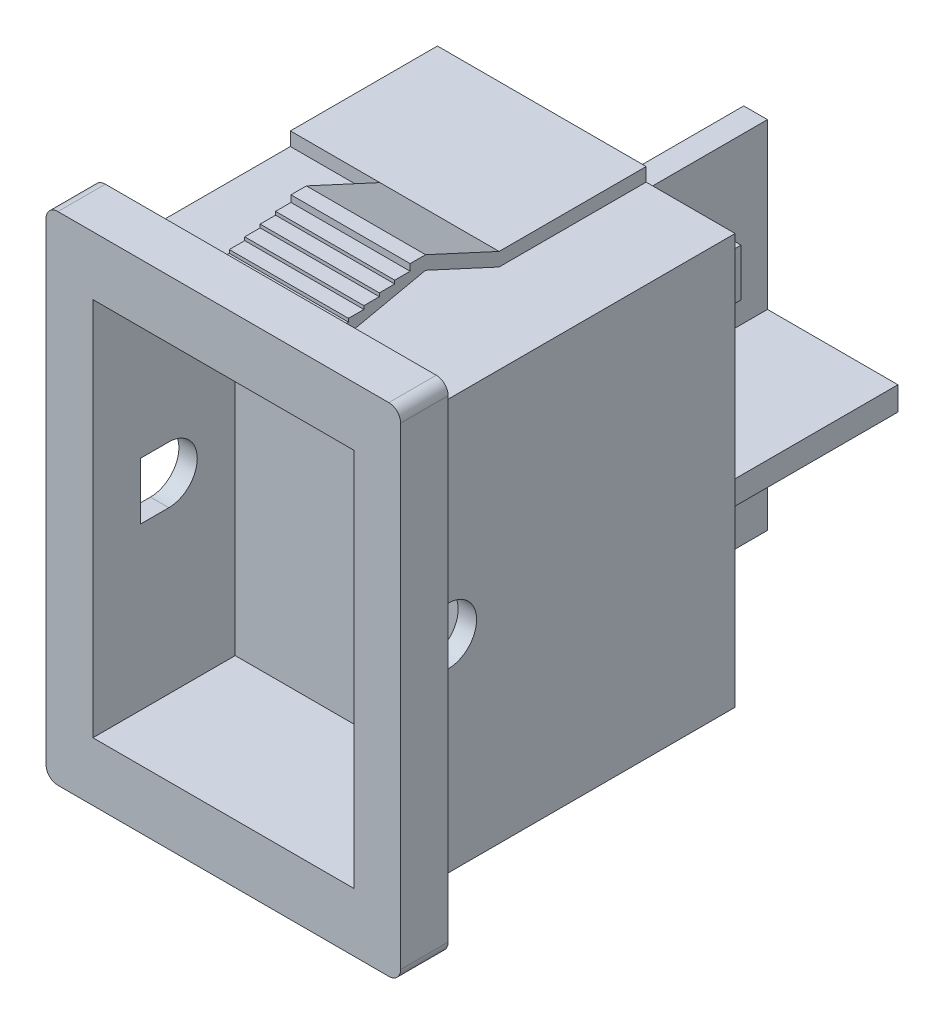
SolidWorks part; units mm, degrees
ref_plane "Front Plane" through (0, 0, 0) normal (0, 0, 1) x (1, 0, 0)
ref_plane "Top Plane" through (0, 0, 0) normal (0, 1, 0) x (1, 0, 0)
ref_plane "Right Plane" through (0, 0, 0) normal (1, 0, 0) x (0, 0, -1)
sketch "Sketch1" plane through (0, 0, 0) normal (0, 0, 1) x (1, 0, 0)
  line L1 (-7.475, 10.475) -> (7.475, 10.475)
  line L2 (-7.475, 10.475) -> (-7.475, -10.475)
  line L3 (-7.475, -10.475) -> (7.475, -10.475)
  line L4 (7.475, 10.475) -> (7.475, -10.475)
  line L5 (-5.5, 8) -> (5.5, 8)
  line L6 (-5.5, 8) -> (-5.5, -8)
  line L7 (-5.5, -8) -> (5.5, -8)
  line L8 (5.5, 8) -> (5.5, -8)
  dimension "D1" = 14.95
  dimension "D2" = 20.95
  dimension "D3" = 11
  dimension "D4" = 16
  dimension "D5" = 10.475
  dimension "D6" = 7.475
  dimension "D7" = 1.975
  dimension "D8" = 2.475
extrude "Boss-Extrude1" add sketch "Sketch1" along normal blind 2
sketch "Sketch2" plane through (0, 0, 0) normal (0, 0, -1) x (-1, 0, 0)
  line L1 (-6.275, 8.65) -> (6.275, 8.65)
  line L2 (-6.275, 8.65) -> (-6.275, -8.65)
  line L3 (-6.275, -8.65) -> (6.275, -8.65)
  line L4 (6.275, 8.65) -> (6.275, -8.65)
  dimension "D1" = 12.55
  dimension "D2" = 17.3
  dimension "D3" = 8.65
  dimension "D4" = 6.275
extrude "Boss-Extrude2" add sketch "Sketch2" along normal blind 13.3
sketch "Sketch3" plane through (-6.275, 0, 0) normal (-1, 0, 0) x (0, 0, 1)
  line L1 (-7.1, 9.22) -> (-13.3, 9.22)
  line L2 (-7.1, 9.22) -> (-7.1, -9.22)
  line L3 (-7.1, -9.22) -> (-13.3, -9.22)
  line L5 (-13.3, 9.22) -> (-13.3, -9.22)
  line L6 (-13.3, 8.65) -> (0, 8.65) construction
  line L7 (0, -8.65) -> (0, 8.65) construction
  line L9 (0, -8.65) -> (0, 8.65)
  line L10 (0, 8.65) -> (-13.3, 8.65)
  line L11 (-13.3, 8.65) -> (-13.3, -8.65)
  line L12 (-13.3, -8.65) -> (0, -8.65)
  line L15 (-13.3, 8.65) -> (-13.3, -8.65) construction
  dimension "D1" = 18.44
  dimension "D3" = 17.3
  dimension "D4" = 0.57
  dimension "D5" = 6.2
  dimension "D6" = 7.1
extrude "Boss-Extrude3" add sketch "Sketch3" against normal blind 8.8
ref_plane "Plane1" through (0, 0, 0) normal (1, 0, 0) x (0, 0, -1)
sketch "Sketch4" plane through (0, 0, 0) normal (1, 0, 0) x (0, 0, -1)
  line L0 (-4.4348, -10.65) -> (15.1231, -10.65) construction
  line L4 (4.9684, -10.65) -> (4.9684, 10.65) construction
  line L5 (-4.4348, 10.65) -> (15.1231, 10.65) construction
  line L6 (4, -13.528) -> (4, 14.734) construction
  line L7 (-5.6758, 0) -> (15.9446, 0) construction
  line L8 (7.1, -9.22) -> (4, -10.65)
  line L9 (7.1, -8.65) -> (4, -10.08)
  line L10 (0, -9.22) -> (4, -10.08)
  line L11 (0, -10.475) -> (0, 10.475) construction
  line L14 (4, -10.65) -> (3.35, -10.65)
  line L15 (2.7, -10.3705) -> (3.35, -10.3705)
  line L16 (3.35, -10.3705) -> (3.35, -10.65)
  line L17 (2.05, -10.2308) -> (2.7, -10.2308)
  line L18 (2.7, -10.2308) -> (2.7, -10.3705)
  line L19 (1.4, -10.091) -> (2.05, -10.091)
  line L20 (2.05, -10.091) -> (2.05, -10.2308)
  line L21 (0.75, -9.9513) -> (1.4, -9.9513)
  line L22 (1.4, -9.9513) -> (1.4, -10.091)
  line L23 (0.75, -9.9513) -> (0.75, -9.8115)
  line L24 (0.75, -9.8115) -> (0, -9.8115)
  line L25 (7.1, -9.22) -> (7.1, -8.65)
  line L26 (0, -9.8115) -> (0, -9.22)
  line L27 (7.1, 9.22) -> (7.1, 8.65)
  line L28 (0.75, 9.8115) -> (0, 9.8115)
  line L29 (0.75, 9.9513) -> (0.75, 9.8115)
  line L30 (1.4, 9.9513) -> (1.4, 10.091)
  line L31 (0.75, 9.9513) -> (1.4, 9.9513)
  line L32 (2.05, 10.091) -> (2.05, 10.2308)
  line L33 (1.4, 10.091) -> (2.05, 10.091)
  line L34 (2.7, 10.2308) -> (2.7, 10.3705)
  line L35 (2.05, 10.2308) -> (2.7, 10.2308)
  line L36 (3.35, 10.3705) -> (3.35, 10.65)
  line L37 (2.7, 10.3705) -> (3.35, 10.3705)
  line L38 (4, 10.65) -> (3.35, 10.65)
  line L39 (0, 9.22) -> (4, 10.08)
  line L40 (7.1, 8.65) -> (4, 10.08)
  line L41 (7.1, 9.22) -> (4, 10.65)
  line L42 (0, 9.8115) -> (0, 9.22)
  point P0 (4.9684, 0)
  dimension "D1" = 21.3
  dimension "D3" = 0.57
  dimension "D9" = 0.1397
  dimension "D10" = 0.1397
  dimension "D11" = 0.75
  dimension "D14" = 15.1231
  dimension "D15" = 15.1231
  dimension "D16" = 4.4348
  dimension "D17" = 4.4348
  dimension "D12" = 4.9684
  dimension "D13" = 9.22
  dimension "D18" = 10.2308
  dimension "D19" = 10.3705
  dimension "D2" = 1.4
  dimension "D4" = 2.05
  dimension "D5" = 2.7
  dimension "D6" = 3.35
  dimension "D7" = 4
  dimension "D8" = 9.8115
extrude "Boss-Extrude4" add sketch "Sketch4" along normal up to surface (2.525 mm away) and the other way blind 2.5 up to face at (2.525, -8.935, -10.2)
sketch "Sketch5" plane through (0, 0, -13.3) normal (0, 0, -1) x (-1, 0, 0)
  line L0 (-6.275, -8.65) -> (-2.525, -8.65) construction
  line L1 (0.5, 6.35) -> (-0.5, 6.35)
  line L2 (0.5, 6.35) -> (0.5, -0.58)
  line L3 (0.5, -8.65) -> (-0.5, -8.65)
  line L4 (-0.5, 6.35) -> (-0.5, -0.58)
  line L5 (0, 8.415) -> (0, -8.415) construction
  line L6 (-2.525, 9.22) -> (6.275, 9.22) construction
  line L7 (-6, -0.58) -> (-0.5, -0.58)
  line L8 (-6, -0.58) -> (-6, -1.58)
  line L9 (-6, -1.58) -> (-0.5, -1.58)
  line L10 (6, -0.58) -> (6, -1.58)
  line L11 (-0.5, -1.58) -> (-0.5, -8.65)
  line L12 (0.5, -0.58) -> (6, -0.58)
  line L13 (0.5, -1.58) -> (0.5, -8.65)
  line L14 (0.5, -1.58) -> (6, -1.58)
  dimension "D1" = 1
  dimension "D2" = 15
  dimension "D3" = 0.5
  dimension "D4" = 1
  dimension "D5" = 12
  dimension "D6" = 6
  dimension "D7" = 10.8
extrude "Boss-Extrude5" add sketch "Sketch5" along normal blind 7.14
sketch "Sketch6" plane through (0, 0, -13.3) normal (0, 0, -1) x (-1, 0, 0)
  line L0 (0.5, -1.58) -> (6, -1.58) construction
  line L1 (0.9829, -1.58) -> (3.4829, -1.58)
  line L2 (0.9829, -1.58) -> (0.9829, -3.58)
  line L3 (0.9829, -8.58) -> (3.4829, -8.58)
  line L4 (3.4829, -1.58) -> (3.4829, -3.58)
  line L5 (0.9829, -6.58) -> (0.9829, -8.58)
  line L6 (0.9829, -3.58) -> (3.4829, -3.58)
  line L8 (0.9829, -6.58) -> (3.4829, -6.58)
  line L10 (3.4829, -6.58) -> (3.4829, -8.58)
  line L11 (0, 12.2791) -> (0, -12.2791) construction
  line L12 (0, 12.342) -> (0, -12.342) construction
  line L13 (-3.4829, -6.58) -> (-3.4829, -8.58)
  line L14 (-0.9829, -8.58) -> (-3.4829, -8.58)
  line L15 (-0.9829, -6.58) -> (-0.9829, -8.58)
  line L16 (-0.9829, -6.58) -> (-3.4829, -6.58)
  line L17 (-3.4829, -1.58) -> (-3.4829, -3.58)
  line L18 (-0.9829, -1.58) -> (-3.4829, -1.58)
  line L19 (-0.9829, -1.58) -> (-0.9829, -3.58)
  line L20 (-0.9829, -3.58) -> (-3.4829, -3.58)
  line L21 (0.5, 6.35) -> (-0.5, 6.35) construction
  line L22 (3.025, 7.35) -> (5.525, 7.35)
  line L23 (3.025, 7.35) -> (3.025, 5.35)
  line L24 (3.025, 5.35) -> (5.525, 5.35)
  line L25 (5.525, 7.35) -> (5.525, 5.35)
  line L30 (6.275, -8.65) -> (6.275, 8.65) construction
  line L31 (-3.025, 5.35) -> (-5.525, 5.35)
  line L32 (-5.525, 7.35) -> (-5.525, 5.35)
  line L33 (-3.025, 7.35) -> (-5.525, 7.35)
  line L34 (-3.025, 7.35) -> (-3.025, 5.35)
  dimension "D1" = 7
  dimension "D2" = 2.5
  dimension "D3" = 3
  dimension "D4" = 2
  dimension "D5" = 2
  dimension "D6" = 2.5
  dimension "D7" = 1
  dimension "D8" = 0.75
extrude "Boss-Extrude6" add sketch "Sketch6" along normal blind 1
sketch "Sketch7" plane through (6.275, 0, 0) normal (1, 0, 0) x (0, 0, -1)
  line L0 (0, 8.65) -> (0, -8.65) construction
  line L1 (1.2, 1.2) -> (0, 1.2)
  line L2 (0, -10.475) -> (0, 10.475) construction
  line L3 (0, 1.2) -> (0, -1.2)
  line L4 (0, -1.2) -> (1.2, -1.2)
  arc A0 (1.2, -1.2) -> (1.2, 1.2) centre (1.2, 0) ccw
  dimension "D1" = 2.4
extrude "Cut-Extrude1" cut sketch "Sketch7" against normal up to surface (12.55 mm away) up to face at (-6.275, 0, -6.875)
sketch "Sketch8" plane through (0, 0, 0) normal (0, 0, 1) x (1, 0, 0)
  line L1 (-5.5, 8) -> (5.5, 8)
  line L2 (-5.5, 8) -> (-5.5, -8)
  line L3 (-5.5, -8) -> (5.5, -8)
  line L4 (5.5, 8) -> (5.5, -8)
extrude "Cut-Extrude2" cut sketch "Sketch8" against normal blind 4
fillet "Fillet1" radius 0.5 4 edges at (-7.475, 10.475, 1) (7.475, 10.475, 1) (7.475, -10.475, 1) (-7.475, -10.475, 1)
equation "\"D5@Sketch1\"=\"D2@Sketch1\"/2"
equation "\"D6@Sketch1\"=\"D1@Sketch1\"/2"
equation "\"D7@Sketch1\"=(\"D1@Sketch1\"-\"D3@Sketch1\")/2"
equation "\"D8@Sketch1\"=(\"D2@Sketch1\"-\"D4@Sketch1\")/2"
equation "\"D3@Sketch2\"=\"D2@Sketch2\"/2"
equation "\"D4@Sketch2\"=\"D1@Sketch2\"/2"
equation "\"D4@Sketch3\"=(\"D1@Sketch3\"-\"D3@Sketch3\")/2"
equation "\"D10@Sketch4\"=\"D9@Sketch4\""
equation "\"D3@Sketch5\"=\"D1@Sketch5\"/2"
equation "\"D6@Sketch5\"=\"D5@Sketch5\"/2"
